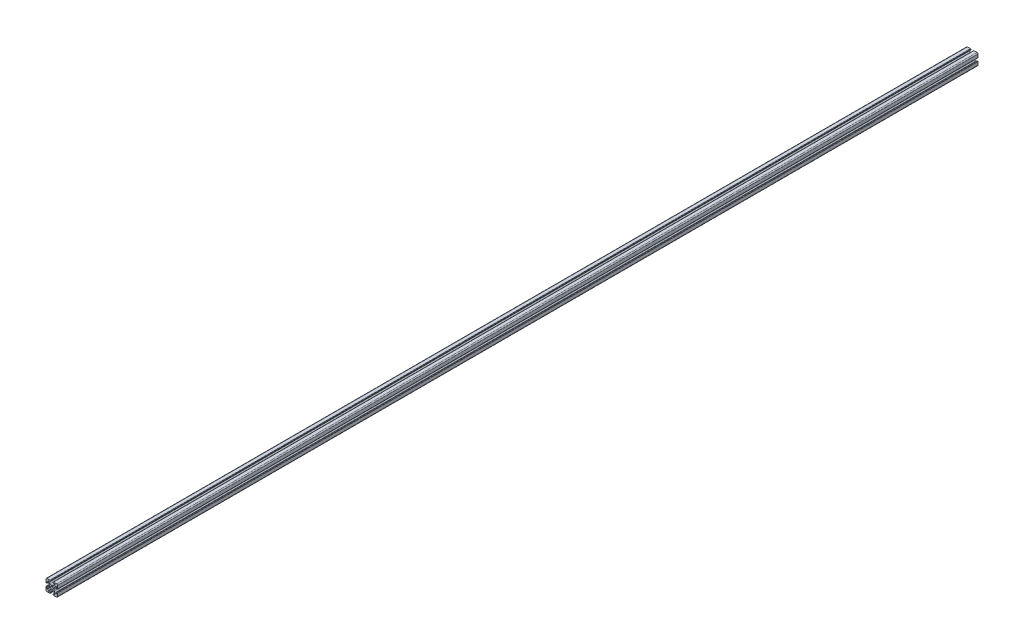
SolidWorks part; units mm, degrees
material "6061 Alloy"
ref_plane "Front Plane" through (0, 0, 0) normal (0, 0, 1) x (1, 0, 0)
ref_plane "Top Plane" through (0, 0, 0) normal (0, 1, 0) x (1, 0, 0)
ref_plane "Right Plane" through (0, 0, 0) normal (1, 0, 0) x (0, 0, -1)
sketch "Sketch2" plane through (0, 0, 0) normal (0, 0, 1) x (1, 0, 0)
  line L0 (0, 10) -> (0, -10) construction
  line L1 (-10, 0) -> (10, 0) construction
  line L2 (2.5, -10) -> (10, -10)
  line L3 (10, -10) -> (10, -2.5)
  line L4 (2.5, -10) -> (2.5, -7.9246)
  line L5 (2.5, -7.9246) -> (6.4571, -7.9246)
  line L6 (6.4571, -7.9246) -> (2.1325, -3.6)
  line L7 (0, 0) -> (10, -10) construction
  line L8 (10, -2.5) -> (7.9246, -2.5)
  line L9 (7.9246, -2.5) -> (7.9246, -6.4571)
  line L10 (7.9246, -6.4571) -> (3.6, -2.1325)
  line L11 (5.7623, -4.2948) -> (4.2948, -5.7623) construction
  circle A0 centre (0, 0) radius 2.15
  arc A1 (5.25, -7.9246) -> (5.6036, -7.0711) centre (5.25, -7.4246) ccw construction
  point P8 (0, -3.6)
  point P16 (5.0286, -5.0286)
  dimension "Center Hole Diameter" = 4.3
  dimension "D3" = 0.5
  dimension "Rail Height" = 20
  dimension "Rail Width" = 20
  dimension "T-Slot Width" = 5
  dimension "Slot Depth" = 6.4
  dimension "Slot Inner Width" = 11.5
sketch "Sketch3" plane through (0, 0, 0) normal (1, 0, 0) x (0, 0, -1)
  line L0 (-800, -10) -> (800, -10) construction
  line L1 (-774.6, 0) -> (774.6, 0) construction
  line L2 (0, 10) -> (0, -10) construction
  line L3 (0, 10) -> (0, -10) construction
  point P6 (-774.6, 0)
  point P8 (774.6, 0)
  dimension "Length" = 1600
  dimension "D1" = 25.4
sketch "Sketch4" plane through (0, 0, 0) normal (0, 0, 1) x (1, 0, 0)
  line L0 (3, -10) -> (8.25, -10)
  line L1 (2.5, -10) -> (10, -10) construction
  line L2 (2.5, -10) -> (2.5, -7.9246) construction
  line L3 (2.5, -7.9246) -> (6.4571, -7.9246) construction
  line L4 (2.5, -8.4246) -> (2.5, -9.5)
  line L5 (3, -7.9246) -> (5.25, -7.9246)
  line L6 (0, -3.6) -> (0.8898, -3.6)
  line L7 (6.4571, -7.9246) -> (2.1325, -3.6) construction
  line L8 (3.0112, -4.4787) -> (5.6036, -7.0711)
  line L9 (10, -10) -> (10, -2.5) construction
  line L10 (7.9246, -6.4571) -> (3.6, -2.1325) construction
  line L11 (7.9246, -2.5) -> (7.9246, -6.4571) construction
  line L12 (7.9246, -5.25) -> (7.9246, -3)
  line L13 (10, -2.5) -> (7.9246, -2.5) construction
  line L14 (8.4246, -2.5) -> (9.5, -2.5)
  line L15 (10, -3) -> (10, -8.25)
  line L16 (7.0711, -5.6036) -> (4.4787, -3.0112)
  line L17 (3.6, 0) -> (3.6, -0.8898)
  line L18 (-10, 0) -> (10, 0) construction
  line L19 (0, -3.6) -> (0, -2.15)
  line L20 (0, 10) -> (0, -10) construction
  line L21 (3.6, 0) -> (2.15, 0)
  arc A0 (2.5, -9.5) -> (3, -10) centre (3, -9.5) ccw
  arc A1 (5.25, -7.9246) -> (5.6036, -7.0711) centre (5.25, -7.4246) ccw construction
  arc A2 (2.5, -8.4246) -> (3, -7.9246) centre (3, -8.4246) cw
  arc A3 (5.25, -7.9246) -> (5.6036, -7.0711) centre (5.25, -7.4246) ccw
  arc A4 (0.8898, -3.6) -> (3.0112, -4.4787) centre (0.8898, -6.6) cw
  arc A5 (8.25, -10) -> (10, -8.25) centre (8.25, -8.25) ccw
  arc A6 (7.0711, -5.6036) -> (7.9246, -5.25) centre (7.4246, -5.25) ccw
  arc A7 (7.9246, -3) -> (8.4246, -2.5) centre (8.4246, -3) cw
  arc A8 (9.5, -2.5) -> (10, -3) centre (9.5, -3) cw
  arc A9 (4.4787, -3.0112) -> (3.6, -0.8898) centre (6.6, -0.8898) cw
  circle A10 centre (0, 0) radius 2.15 construction
  arc A11 (0, -2.15) -> (2.15, 0) centre (0, 0) ccw
  dimension "D1" = 1.75
  dimension "D2" = 3
extrude "Boss-Extrude1" add sketch "Sketch4" along normal mid plane 1600
mirror "Mirror1" about plane through (0, 0, 0) normal (1, 0, 0) of bodies 134
mirror "Mirror2" about plane through (0, 0, 0) normal (0, 1, 0) of bodies 135
equation "\"D3@Sketch2\"=\"T-Slot Width@Sketch2\"*0.1"
equation "\"D1@Sketch4\"=\"D3@Sketch2\"*3.5"
equation "\"D2@Sketch4\"=\"D3@Sketch2\"*6"
equation "\"D1@Boss-Extrude1\"=\"Length@Sketch3\""
